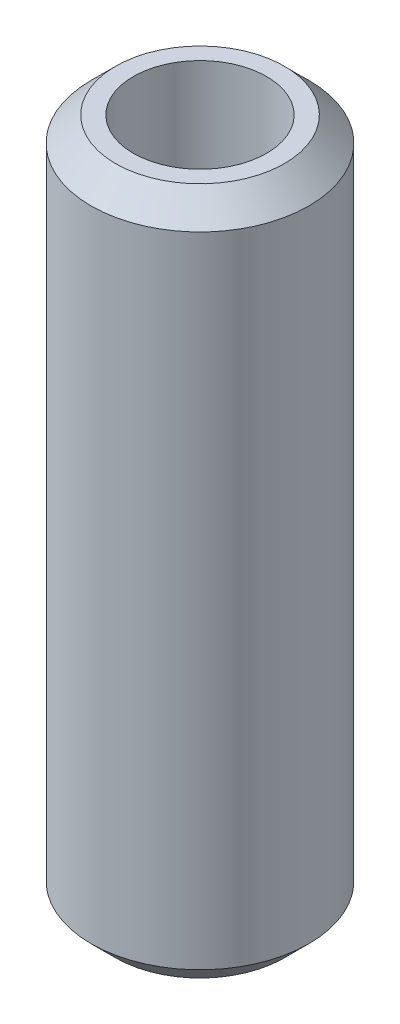
SolidWorks part; units mm, degrees
ref_plane "Front Plane" through (0, 0, 0) normal (0, 0, 1) x (1, 0, 0)
ref_plane "Top Plane" through (0, 0, 0) normal (0, 1, 0) x (1, 0, 0)
ref_plane "Right Plane" through (0, 0, 0) normal (1, 0, 0) x (0, 0, -1)
sketch "Sketch1" plane through (0, 0, 0) normal (0, 1, 0) x (1, 0, 0)
  circle A0 centre (0, 0) radius 7.5
  dimension "SHAFT_OD" = 15
extrude "Boss-Extrude1" add sketch "Sketch1" along normal blind 47.393
sketch "Sketch2" plane through (0, 0, 0) normal (0, 1, 0) x (1, 0, 0)
  circle A0 centre (0, 0) radius 4.5886
  dimension "BORE_D" = 9.1772
extrude "Cut-Extrude1" cut sketch "Sketch2" along normal through all
chamfer "Chamfer1" distance 1.6846 angle 45 2 edges at (0, 47.393, 7.5) (0, 0, 7.5)
